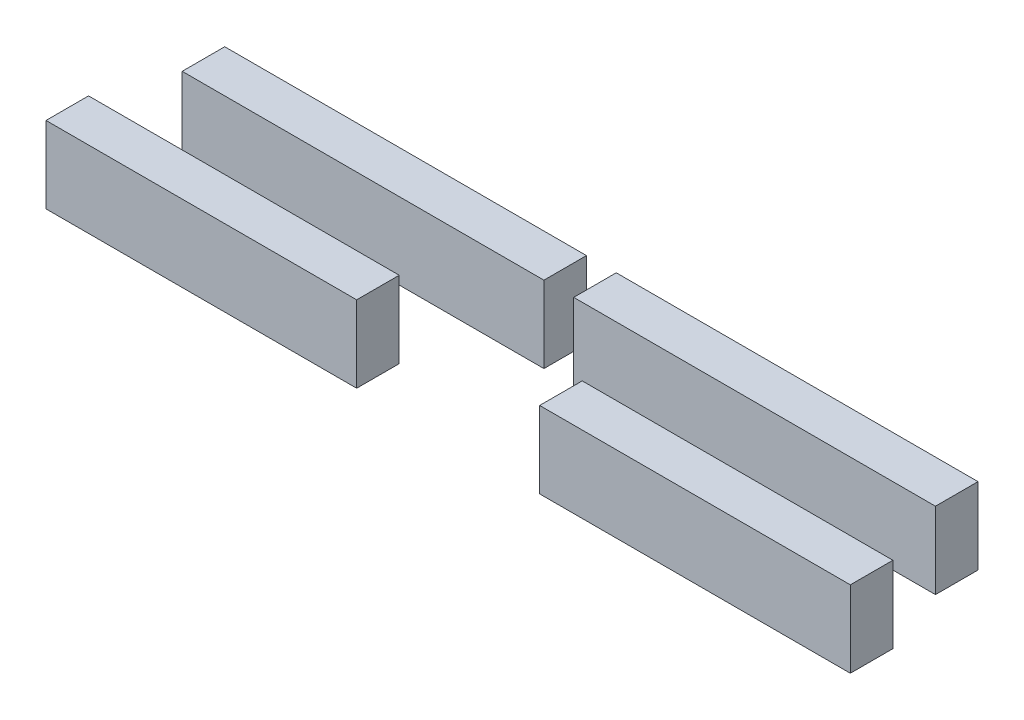
SolidWorks part; units mm, degrees
ref_plane "Front Plane" through (0, 0, 0) normal (0, 0, 1) x (1, 0, 0)
ref_plane "Top Plane" through (0, 0, 0) normal (0, 1, 0) x (1, 0, 0)
ref_plane "Right Plane" through (0, 0, 0) normal (1, 0, 0) x (0, 0, -1)
sketch "Sketch1" plane through (0, 0, 0) normal (0, 1, 0) x (1, 0, 0)
  line L0 (60.75, 9.5) -> (97.25, 9.5)
  line L1 (2.75, 9.5) -> (39.25, 9.5)
  line L2 (2.75, 9.5) -> (2.75, 4.5)
  line L3 (2.75, 4.5) -> (39.25, 4.5)
  line L4 (39.25, 9.5) -> (39.25, 4.5)
  line L5 (0, 0) -> (100, 0) construction
  line L6 (0, 0) -> (0, 75) construction
  line L7 (0, 75) -> (100, 75) construction
  line L8 (100, 0) -> (100, 75) construction
  line L9 (60.75, 9.5) -> (60.75, 4.5)
  line L10 (60.75, 4.5) -> (97.25, 4.5)
  line L11 (97.25, 9.5) -> (97.25, 4.5)
  line L12 (51.75, 22.5) -> (94.25, 22.5)
  line L13 (5.75, 22.5) -> (48.25, 22.5)
  line L14 (5.75, 22.5) -> (5.75, 17.5)
  line L15 (5.75, 17.5) -> (48.25, 17.5)
  line L16 (48.25, 22.5) -> (48.25, 17.5)
  line L17 (51.75, 22.5) -> (51.75, 17.5)
  line L18 (51.75, 17.5) -> (94.25, 17.5)
  line L19 (94.25, 22.5) -> (94.25, 17.5)
extrude "Boss-Extrude1" add sketch "Sketch1" along normal blind 9
